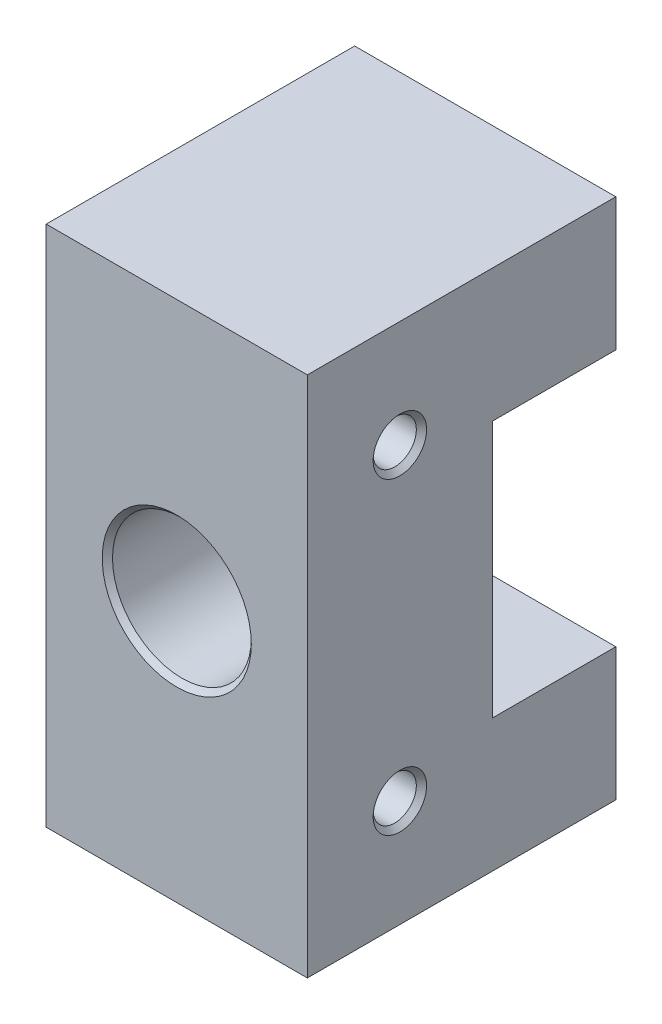
SolidWorks part; units mm, degrees
material "6061 Alloy"
ref_plane "Front Plane" through (0, 0, 0) normal (0, 0, 1) x (1, 0, 0)
ref_plane "Top Plane" through (0, 0, 0) normal (0, 1, 0) x (1, 0, 0)
ref_plane "Right Plane" through (0, 0, 0) normal (1, 0, 0) x (0, 0, -1)
sketch "Sketch1" plane through (0, 0, 0) normal (0, 0, 1) x (1, 0, 0)
  line L1 (-12.7, 25.4) -> (12.7, 25.4)
  line L2 (-12.7, 25.4) -> (-12.7, -25.4)
  line L3 (-12.7, -25.4) -> (12.7, -25.4)
  line L4 (12.7, 25.4) -> (12.7, -25.4)
  line L5 (-12.7, 25.4) -> (12.7, -25.4) construction
  line L6 (-12.7, -25.4) -> (12.7, 25.4) construction
  point P0 (0, 0)
  dimension "D1" = 50.8
  dimension "D2" = 25.4
extrude "Boss-Extrude1" add sketch "Sketch1" along normal blind 30
sketch "Sketch2" plane through (0, 0, 0) normal (0, 0, 1) x (1, 0, 0)
  line L0 (-12.7, 25.4) -> (-12.7, -25.4) construction
  line L1 (12.7, 12.5) -> (-12.7, 12.5)
  line L2 (12.7, 12.5) -> (12.7, -12.5)
  line L3 (12.7, -12.5) -> (-12.7, -12.5)
  line L4 (-12.7, 12.5) -> (-12.7, -12.5)
  line L5 (12.7, 12.5) -> (-12.7, -12.5) construction
  line L6 (12.7, -12.5) -> (-12.7, 12.5) construction
  point P0 (0, 0)
  dimension "D1" = 25
extrude "Cut-Extrude1" cut sketch "Sketch2" along normal blind 12
hole_wizard "M12 Clearance Hole1" positions "Sketch7" profile "Sketch8" hole size "M12" standard "ANSI Metric" end condition up to next
sketch "Sketch7" plane through (0, 0, 12) normal (0, 0, -1) x (-1, 0, 0)
  point P0 (0, 0)
sketch "Sketch8" plane through (0, 0, 12) normal (1, 0, 0) x (0, 1, 0)
  line L0 (0, 0) -> (0, 18)
  line L1 (0, 18) -> (6.75, 18)
  line L2 (6.75, 18) -> (6.75, 0)
  line L5 (6.75, 0) -> (0, 0)
  line L11 (0, -6.35) -> (0, 107.95) construction
  dimension "Thru Hole Dia." = 13.5
  dimension "Thru Hole Depth" = 18
hole_wizard "M5x0.8 Tapped Hole1" positions "Sketch10" profile "Sketch11" tap size "M5x0.8" standard "ANSI Metric"
sketch "Sketch10" plane through (12.7, 0, 0) normal (1, 0, 0) x (0, 0, -1)
  line L0 (-21, 15) -> (-21, -15) construction
  line L2 (-30, 0) -> (-12, 0) construction
  line L3 (-30, -25.4) -> (-30, 25.4) construction
  line L4 (-12, -12.5) -> (-12, 12.5) construction
  point P0 (-21, 15)
  point P2 (-21, -15)
  point P16 (-21, 0)
  dimension "D1" = 30
sketch "Sketch11" plane through (12.7, 15, 21) normal (0, 1, 0) x (0, 0, -1)
  line L0 (0, 0) -> (0, 12)
  line L1 (0, 12) -> (2.1, 10.7382)
  line L2 (2.1, 10.7382) -> (2.1, 0)
  line L5 (2.1, 0) -> (0, 0)
  line L10 (0, 12) -> (-2.1, 10.7382) construction
  line L11 (0, -6.35) -> (0, 107.95) construction
  dimension "Tap Drill Dia." = 4.2
  dimension "Tap Drill Depth" = 12
  dimension "Drill Angle" = 118
cosmetic thread "Hole Thread5" parameters "D1"=10, "D2"=5
cosmetic thread "Hole Thread6" parameters "D1"=10, "D2"=5
mirror "Mirror1" about plane through (0, 0, 0) normal (1, 0, 0) of "M5x0.8 Tapped Hole1"
cosmetic thread "Hole Thread7" parameters "D1"=10, "D2"=5
cosmetic thread "Hole Thread8" parameters "D1"=10, "D2"=5
chamfer "Chamfer1 0.5 mm" distance 0.5 angle 45 6 edges at (6.75, 0, 30) (-6.75, 0, 12) (12.7, -15, 18.9) (12.7, 15, 18.9) (-12.7, -15, 23.1) (-12.7, 15, 23.1)
equation "\"D1@Sketch1\"=2in"
